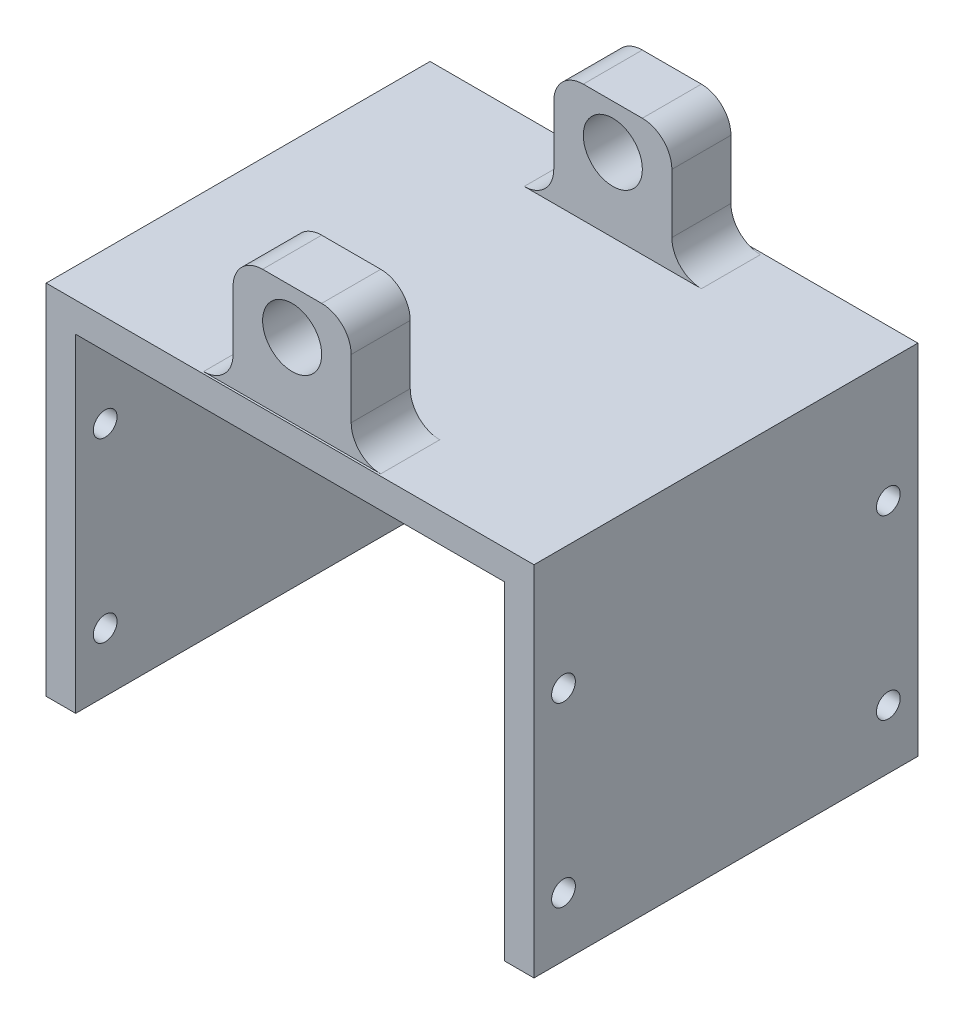
SolidWorks part; units mm, degrees
ref_plane "Front Plane" through (0, 0, 0) normal (0, 0, 1) x (1, 0, 0)
ref_plane "Top Plane" through (0, 0, 0) normal (0, 1, 0) x (1, 0, 0)
ref_plane "Right Plane" through (0, 0, 0) normal (1, 0, 0) x (0, 0, -1)
sketch "Sketch1" plane through (0, 0, 0) normal (0, 0, 1) x (1, 0, 0)
  line L0 (98.552, 0) -> (104.902, 0)
  line L1 (0, 76.962) -> (104.902, 76.962)
  line L2 (0, 76.962) -> (0, 0)
  line L3 (0, 0) -> (6.35, 0)
  line L4 (104.902, 76.962) -> (104.902, 0)
  line L5 (6.35, 70.612) -> (98.552, 70.612)
  line L6 (6.35, 70.612) -> (6.35, 0)
  line L8 (98.552, 70.612) -> (98.552, 0)
  line L9 (39.751, 102.362) -> (65.151, 102.362)
  line L10 (39.751, 102.362) -> (39.751, 76.962)
  line L11 (39.751, 76.962) -> (65.151, 76.962)
  line L12 (65.151, 102.362) -> (65.151, 76.962)
  circle A0 centre (52.451, 92.837) radius 6.35
  dimension "D11" = 12.7
  dimension "D1" = 92.202
  dimension "D2" = 70.612
  dimension "D3" = 6.35
  dimension "D4" = 6.35
  dimension "D5" = 6.35
  dimension "D6" = 25.4
  dimension "D7" = 33.401
  dimension "D8" = 25.4
  dimension "D9" = 9.525
  dimension "D10" = 12.7
extrude "Boss-Extrude1" add sketch "Sketch1" along normal blind 82.55 contours L12 L9 L10 L1 A0 | L5 L8 L0 L4 L1 L2 L3 L6 region at (99.8531, 35.306, 0) region at (52.451, 77.3212, 0)
fillet "Fillet1" radius 6.35 4 edges at (65.151, 102.362, 41.275) (39.751, 102.362, 41.275) (65.151, 76.962, 41.275) (39.751, 76.962, 41.275)
ref_plane "Plane1" through (0, 108.712, 0) normal (0, 1, 0) x (1, 0, 0)
sketch "Sketch3" plane through (0, 108.712, 0) normal (0, 1, 0) x (1, 0, 0)
  line L0 (0, -82.55) -> (33.401, -82.55) construction
  line L1 (-11.726, -82.1055) -> (124.8825, -82.1055)
  line L2 (-11.726, -69.4055) -> (-11.726, -13.1445)
  line L3 (-11.726, -13.1445) -> (124.8825, -13.1445)
  line L4 (124.8825, -69.4055) -> (124.8825, -13.1445)
  line L5 (124.8825, -0.4445) -> (-11.726, -0.4445)
  line L6 (124.8825, -13.1445) -> (124.8825, -69.4055)
  line L7 (124.8825, -69.4055) -> (-11.726, -69.4055)
  line L8 (-11.726, -13.1445) -> (-11.726, -69.4055)
  line L10 (-11.726, -82.1055) -> (124.8825, -82.1055)
  line L11 (-11.726, -82.1055) -> (-11.726, -106.365)
  line L12 (-11.726, -106.365) -> (124.8825, -106.365)
  line L13 (124.8825, -82.1055) -> (124.8825, -106.365)
  line L14 (-11.726, -0.4445) -> (124.8825, -0.4445)
  line L15 (-11.726, -0.4445) -> (-11.726, 27.3507)
  line L16 (-11.726, 27.3507) -> (124.8825, 27.3507)
  line L17 (124.8825, -0.4445) -> (124.8825, 27.3507)
  dimension "D1" = 68.961
  dimension "D2" = 68.961
  dimension "D3" = 12.7
  dimension "D4" = 0.4445
extrude "Cut-Extrude3" cut sketch "Sketch3" against normal blind 31.75 contours L5 L17 L16 L15 | L7 L4 L3 L2 | L13 L1 L11 L12 region at (56.5783, 108.712, 94.2352) region at (56.5783, 108.712, 41.275) region at (56.5783, 108.712, -13.4531)
sketch "Sketch4" plane through (0, 0, 0) normal (-1, 0, 0) x (0, 0, 1)
  line L1 (0, 76.962) -> (0, 0) construction
  line L2 (82.55, 0) -> (0, 0) construction
  circle A0 centre (6.35, 50.8) radius 2.5527
  circle A1 centre (76.2, 50.8) radius 2.5527
  circle A2 centre (76.2, 12.7) radius 2.5527
  circle A3 centre (6.35, 12.7) radius 2.5527
  dimension "D1" = 5.1054
  dimension "D2" = 69.85
  dimension "D3" = 6.35
  dimension "D4" = 12.7
  dimension "D5" = 50.8
hole_wizard "Tap Drill for 1/4-20 Tap1" positions "Sketch6" profile "Sketch5" hole size "1/4-20" standard "ANSI Inch" end condition through all
sketch "Sketch6" plane through (0, 0, 0) normal (-1, 0, 0) x (0, 0, 1)
  point P0 (6.35, 50.8)
  point P3 (6.35, 12.7)
  point P6 (76.2, 12.7)
  point P9 (76.2, 50.8)
sketch "Sketch5" plane through (0, 50.8, 6.35) normal (0, 1, 0) x (0, 0, 1)
  line L0 (0, 0) -> (0, 104.902)
  line L1 (0, 104.902) -> (2.5527, 104.902)
  line L2 (2.5527, 104.902) -> (2.5527, 0)
  line L5 (2.5527, 0) -> (0, 0)
  line L11 (0, -6.35) -> (0, 107.95) construction
  dimension "Thru Hole Dia." = 5.1054
  dimension "Thru Hole Depth" = 104.902
